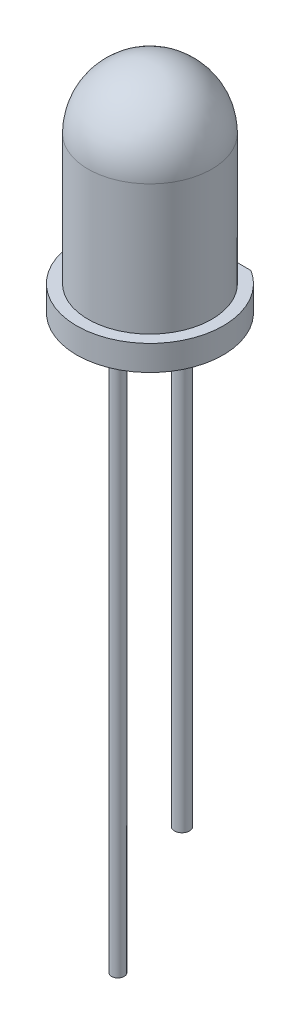
SolidWorks part; units mm, degrees
note: The reader was unsure of these and kept them because the rebuilt part matched: shared geometry of "Sketch3<3>".
ref_plane "Front Plane" through (0, 0, 0) normal (0, 0, 1) x (1, 0, 0)
ref_plane "Top Plane" through (0, 0, 0) normal (0, 1, 0) x (1, 0, 0)
ref_plane "Right Plane" through (0, 0, 0) normal (1, 0, 0) x (0, 0, -1)
sketch "Sketch1" plane through (0, 0, 0) normal (1, 0, 0) x (0, 0, -1)
  line L0 (0, 0) -> (0, 8.6)
  line L1 (0, 0) -> (2.9, 0)
  line L2 (2.9, 0) -> (2.9, 1)
  line L3 (2.45, 6.15) -> (2.45, 1)
  line L4 (2.45, 1) -> (2.9, 1)
  arc A0 (2.45, 6.15) -> (0, 8.6) centre (0, 6.15) ccw
  dimension "D4" = 4.9
  dimension "D1" = 8.6
  dimension "D2" = 2.9
  dimension "D3" = 1
revolve "Revolve1" add sketch "Sketch1" angle 360 about L0
sketch "Sketch2" plane through (0, 1, 0) normal (0, 1, 0) x (1, 0, 0)
  line L0 (0, 2.45) -> (-2.0008, 2.45)
  line L1 (-2.0008, 2.45) -> (-0.0418, 4.409)
  line L2 (-0.0418, 4.409) -> (3.1239, 2.45)
  line L3 (3.1239, 2.45) -> (0, 2.45)
  circle A0 centre (0, 0) radius 2.45 construction
extrude "Cut-Extrude1" cut sketch "Sketch2" against normal blind 10
sketch "Sketch3" plane through (0, 0, 0) normal (1, 0, 0) x (0, 0, -1)
  line L1 (1.27, 0) -> (1.27, -18.2557)
  line L2 (-2.9, 0) -> (2.45, 0) construction
  line L3 (-1.27, 0) -> (-1.27, -22)
  dimension "D1" = 2.54
  dimension "D2" = 18.2557
  dimension "D3" = 22
sweep "Sweep1" add path "Sketch3" circular profile diameter 0.6 parameters "D3"=0.6
sweep "Sweep2" add path "Sketch3<3>" circular profile diameter 0.5 parameters "D3"=0.5
sketch "Sketch3<3>" plane through (0, 0, 0) normal (1, 0, 0) x (0, 0, -1) same geometry as "Sketch3"
